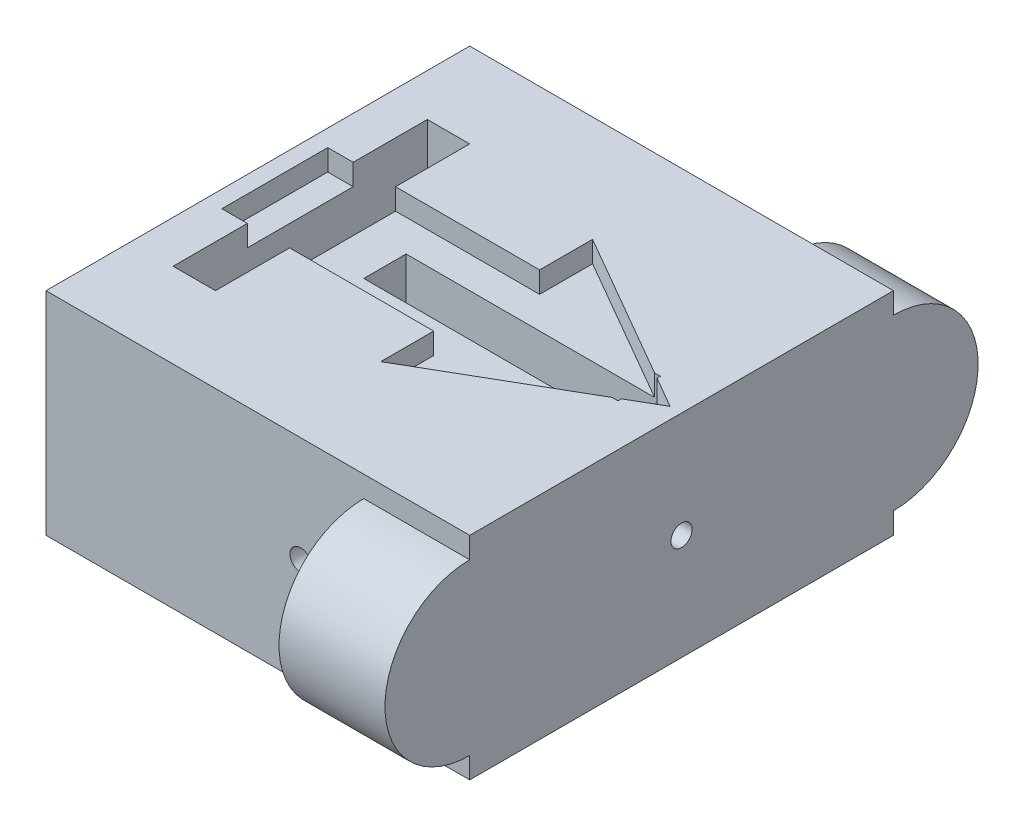
SolidWorks part; units mm, degrees
ref_plane "Front Plane" through (0, 0, 0) normal (0, 0, 1) x (1, 0, 0)
ref_plane "Top Plane" through (0, 0, 0) normal (0, 1, 0) x (1, 0, 0)
ref_plane "Right Plane" through (0, 0, 0) normal (1, 0, 0) x (0, 0, -1)
sketch "Sketch1" plane through (0, 0, 0) normal (0, 1, 0) x (1, 0, 0)
  line L1 (100, -100) -> (-100, -100)
  line L2 (100, -100) -> (100, 100)
  line L3 (100, 100) -> (-100, 100)
  line L4 (-100, -100) -> (-100, 100)
  line L5 (100, -100) -> (-100, 100) construction
  line L6 (100, 100) -> (-100, -100) construction
  point P0 (0, 0)
  dimension "D1" = 200
  dimension "D2" = 200
extrude "Boss-Extrude2" add sketch "Sketch1" along normal blind 100
sketch "Sketch2" plane through (100, 0, 0) normal (-1, 0, 0) x (0, 0, 1)
  line L0 (100, 100) -> (100, 0) construction
  line L1 (-100, 100) -> (-100, 0) construction
  circle A0 centre (100, 50) radius 40
  circle A1 centre (-100, 50) radius 40
  dimension "D1" = 80
extrude "Boss-Extrude3" add sketch "Sketch2" along normal blind 50
sketch "Sketch3" plane through (0, 100, 0) normal (0, 1, 0) x (1, 0, 0)
  line L0 (8, 25) -> (8, 50)
  line L1 (8, -25) -> (-92, -25) construction
  line L2 (8, -25) -> (8, 25) construction
  line L3 (8, 25) -> (-92, 25) construction
  line L4 (-92, -25) -> (-92, 25) construction
  line L5 (8, -25) -> (-92, 25) construction
  line L6 (8, 25) -> (-92, -25) construction
  line L7 (8, 50) -> (94.6025, 0)
  line L8 (94.6025, 0) -> (8, -50)
  line L9 (8, -50) -> (8, -25)
  line L10 (8, -25) -> (-92, -25)
  line L11 (-92, -25) -> (-92, 25)
  line L12 (-92, 25) -> (8, 25)
  line L13 (-100, 100) -> (-100, -100) construction
  point P0 (-42, 0)
  dimension "D1" = 50
  dimension "D2" = 100
  dimension "D3" = 100
  dimension "D4" = 60
  dimension "D5" = 8
extrude "Cut-Extrude1" cut sketch "Sketch3" against normal blind 10
sketch "Sketch4" plane through (0, 100, 0) normal (0, 1, 0) x (1, 0, 0)
  line L0 (-100, 100) -> (-100, -100) construction
  line L1 (80, -10) -> (-40, -10)
  line L2 (80, -10) -> (80, 10)
  line L3 (80, 10) -> (-40, 10)
  line L4 (-40, -10) -> (-40, 10)
  line L5 (80, -10) -> (-40, 10) construction
  line L6 (80, 10) -> (-40, -10) construction
  line L7 (100, -100) -> (100, 100) construction
  line L8 (-80, -60) -> (-60, -60)
  line L9 (-80, -60) -> (-80, 60)
  line L10 (-80, 60) -> (-60, 60)
  line L11 (-60, -60) -> (-60, 60)
  line L12 (-80, -60) -> (-60, 60) construction
  line L13 (-80, 60) -> (-60, -60) construction
  point P0 (20, 0)
  point P6 (-70, 0)
  point P11 (0, 0)
  point P12 (0, 0)
  point P15 (0, 0)
  point P16 (47.2605, -10.0412)
  point P17 (44.5829, -20.7518)
  point P19 (31.9979, 0)
  dimension "D1" = 120
  dimension "D2" = 20
  dimension "D3" = 120
  dimension "D4" = 20
  dimension "D5" = 20
  dimension "D6" = 20
extrude "Cut-Extrude2" cut sketch "Sketch4" against normal through all
ref_point "Point2"
sketch "Sketch5" plane through (0, 0, 100) normal (0, 0, 1) x (1, 0, 0)
  line L0 (-100, 100) -> (-100, 0) construction
  circle A0 centre (20.1472, 50) radius 5
  point P2 (-100, 50)
  point P3 (0, 0)
  point P6 (-27.8589, 50)
  point P8 (0, 0)
  point P9 (0, 0)
  point P11 (0, 0)
  dimension "D1" = 10
extrude "Cut-Extrude3" cut sketch "Sketch5" against normal through all
sketch "Sketch6" plane through (-100, 0, 0) normal (-1, 0, 0) x (0, 0, 1)
  line L1 (-100, 100) -> (-100, 0) construction
  circle A0 centre (0, 50) radius 5
  point P2 (0, 0)
  point P5 (-100, 50)
  dimension "D1" = 10
extrude "Cut-Extrude4" cut sketch "Sketch6" against normal through all
ref_plane "Plane1" through (-70, 0, 0) normal (-1, 0, 0) x (0, 0, 1)
